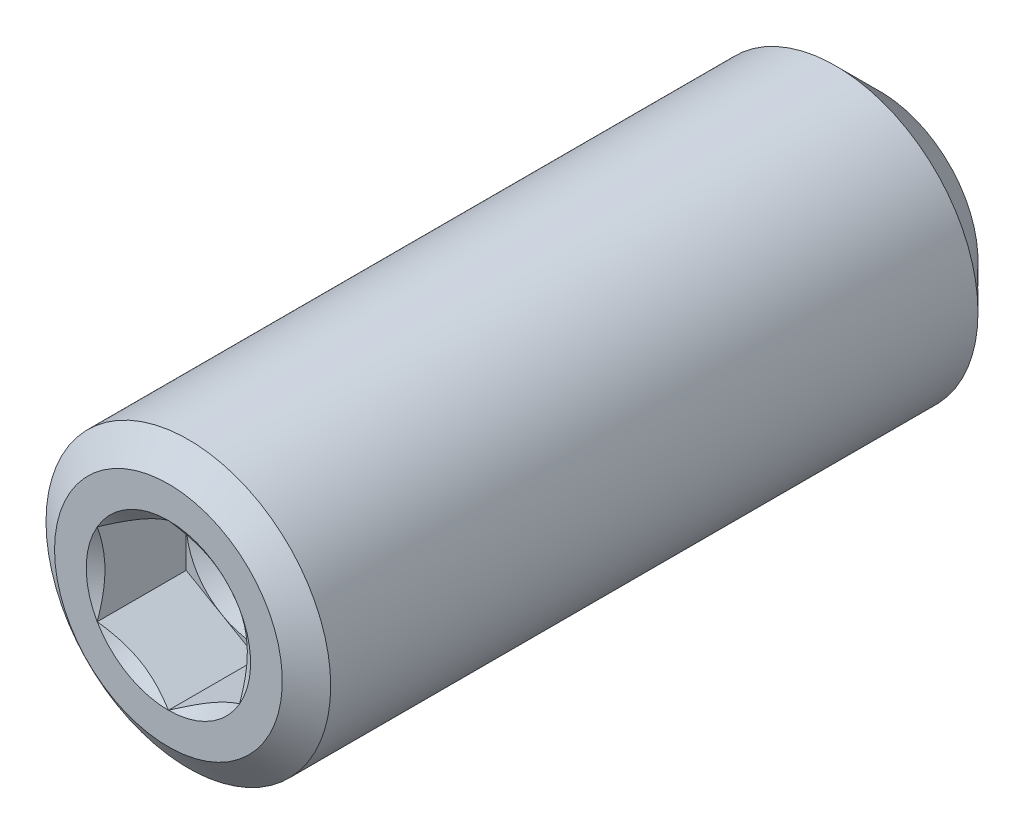
SolidWorks part; units mm, degrees
ref_plane "Front" through (0, 0, 0) normal (0, 0, 1) x (1, 0, 0)
ref_plane "Top" through (0, 0, 0) normal (0, 1, 0) x (1, 0, 0)
ref_plane "Right" through (0, 0, 0) normal (1, 0, 0) x (0, 0, -1)
sketch "Sketch22" plane through (0, 0, 0) normal (1, 0, 0) x (0, 0, -1)
  line L0 (-10, 0) -> (-10, 3.2)
  line L1 (-10, 3.2) -> (-9.4398, 4)
  line L2 (-9.4398, 4) -> (8.75, 4)
  line L3 (8.75, 4) -> (10, 2.75)
  line L4 (-0.3449, 4) -> (-0.3449, -4) construction
  line L5 (10, 0) -> (-10, 0)
  line L6 (-10, 3.2) -> (-10, -3.2) construction
  line L7 (10, 0) -> (10, 2.75)
  point P11 (-0.3449, 0)
  dimension "D1" = 6.4
  dimension "Dia" = 8
  dimension "D2" = 1.25
  dimension "Length" = 20
  dimension "D3" = 35
  dimension "D6" = 45
revolve "Revolve1" add sketch "Sketch22" angle 360 about L5
ref_plane "Plane1" through (0, 0, -10) normal (0, 0, 1) x (1, 0, 0)
sketch "Sketch27" plane through (0, 0, -10) normal (0, 0, 1) x (1, 0, 0)
  circle A0 centre (0, 0) radius 4 construction
  circle A1 centre (0, 0) radius 4
curve "Helix/Spiral1" pitch 1.25 height 21.25 turns 17
sketch "Sketch28" plane through (0, 0, 0) normal (1, 0, 0) x (0, 0, -1)
  line L0 (10, 4) -> (11.0937, 4)
  line L1 (11.0937, 4) -> (10.625, 3.1881)
  line L2 (10.625, 3.1881) -> (10.4687, 3.1881)
  line L3 (10.4687, 3.1881) -> (10, 4)
  line L4 (10.2344, 3.5941) -> (10.8594, 3.5941) construction
  line L6 (-9.4398, 4) -> (8.75, 4) construction
  dimension "D1" = 0.1562
  dimension "D2" = 0.625
  dimension "D3" = 60
sweep "Cut-Sweep2" [suppressed] cut profiles "Sketch28" path "Helix/Spiral1"
sketch "Sketch23" plane through (0, 0, 10) normal (0, 0, 1) x (1, 0, 0)
  line L1 (0, 2.3094) -> (-2, 1.1547)
  line L2 (-2, 1.1547) -> (-2, -1.1547)
  line L3 (-2, -1.1547) -> (0, -2.3094)
  line L4 (0, -2.3094) -> (2, -1.1547)
  line L5 (2, -1.1547) -> (2, 1.1547)
  line L6 (2, 1.1547) -> (0, 2.3094)
  circle A0 centre (0, 0) radius 2 construction
  dimension "Hex" = 4
extrude "Cut-Extrude10" cut sketch "Sketch23" against normal blind 2.5
sketch "Sketch24" plane through (0, 0, 10) normal (0, 0, 1) x (1, 0, 0)
  circle A0 centre (0, 0) radius 2.3094
extrude "Cut-Extrude11" cut sketch "Sketch24" against normal through all draft 55
sketch "Sketch26" plane through (0, 0, 7.5) normal (0, 0, 1) x (1, 0, 0)
  circle A0 centre (0, 0) radius 2 construction
  circle A1 centre (0, 0) radius 2
extrude "Cut-Extrude12" cut sketch "Sketch26" against normal through all draft 60
sketch "Sketch30" plane through (0, 0, 0) normal (1, 0, 0) x (0, 0, -1)
  line L0 (-9.4398, 4) -> (8.75, 4) construction
  line L1 (-10, 0) -> (-10, 3.2) construction
  line L2 (10, 0) -> (10, 2.75) construction
  point P0 (-10, 4)
  point P1 (10, 4)
  point P2 (10, -4)
  point P11 (6.875, -4)
  dimension "D1" = 3.125
equation "\"D1@Sketch28\" = \"D4@Helix/Spiral1\" * .125"
equation "\"D2@Sketch28\" = \"D4@Helix/Spiral1\" * .5"
equation "\"D3@Helix/Spiral1\" = \"Length@Sketch22\" + \"D4@Helix/Spiral1\""
equation "\"D1@Sketch30\" = \"D4@Helix/Spiral1\" * 2.5"
equation "\"hex Depth@Cut-Extrude10\" = \"Hex@Sketch23\" * .625"
equation "\"D1@Sketch22\" = \"Dia@Sketch22\" * .8"
equation "\"D2@Sketch22\" = \"D4@Helix/Spiral1\""
